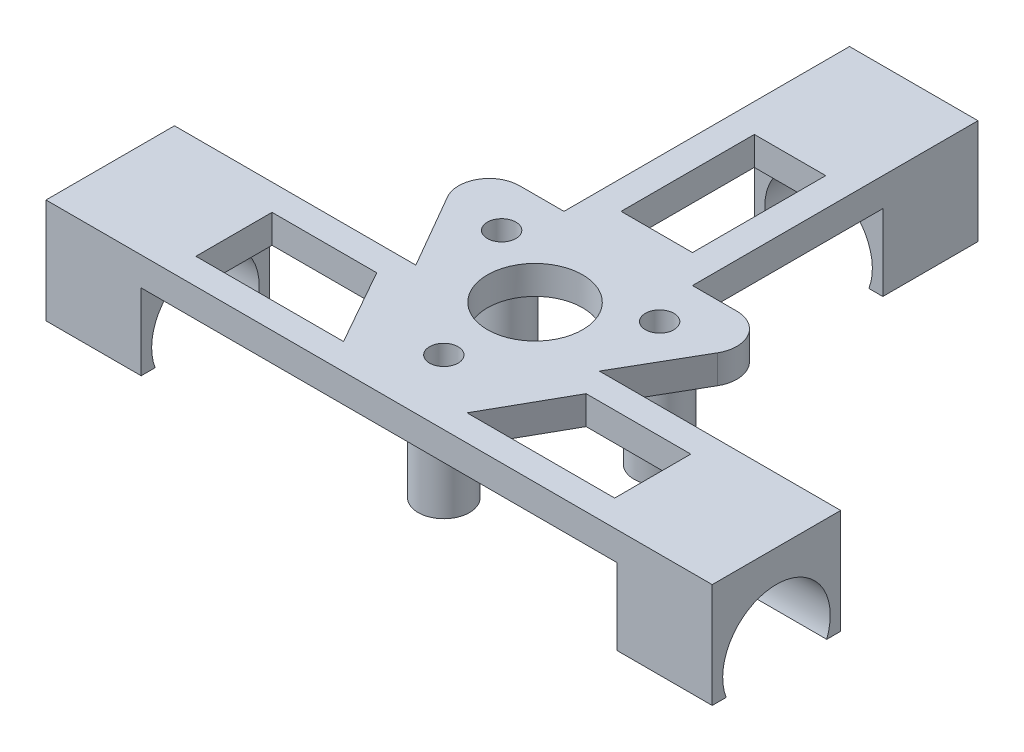
SolidWorks part; units mm, degrees
ref_plane "Front Plane" through (0, 0, 0) normal (0, 0, 1) x (1, 0, 0)
ref_plane "Top Plane" through (0, 0, 0) normal (0, 1, 0) x (1, 0, 0)
ref_plane "Right Plane" through (0, 0, 0) normal (1, 0, 0) x (0, 0, -1)
sketch "Sketch1" plane through (0, 0, 0) normal (0, 1, 0) x (1, 0, 0)
  line L0 (0, 0) -> (16.6, 0) construction
  line L1 (16.6, 0) -> (8.3, -14.376) construction
  line L2 (8.3, -14.376) -> (0, 0) construction
  line L3 (8.3, 0) -> (8.3, -14.376) construction
  line L4 (-3.1177, 5) -> (19.7177, 5)
  line L5 (22.489, 0.2) -> (11.0713, -19.576)
  line L6 (5.5287, -19.576) -> (-5.889, 0.2)
  line L7 (25.2603, 5) -> (8.3, -24.376) construction
  line L8 (8.3, -24.376) -> (-8.6603, 5) construction
  line L9 (-8.6603, 5) -> (25.2603, 5) construction
  circle A0 centre (0, 0) radius 1.5
  circle A1 centre (16.6, 0) radius 1.5
  circle A2 centre (8.3, -14.376) radius 1.5
  arc A3 (11.0713, -19.576) -> (5.5287, -19.576) centre (8.3, -17.976) cw
  arc A4 (22.489, 0.2) -> (19.7177, 5) centre (19.7177, 1.8) ccw
  arc A5 (-5.889, 0.2) -> (-3.1177, 5) centre (-3.1177, 1.8) cw
  dimension "D3" = 3
  dimension "D4" = 3
  dimension "D5" = 3
  dimension "D7" = 3.2
  dimension "D1" = 16.6
  dimension "D2" = 16.6
  dimension "D6" = 5
extrude "Caster Base" add sketch "Sketch1" along normal blind 3
sketch "Sketch2" plane through (0, 0, 0) normal (0, -1, 0) x (1, 0, 0)
  circle A0 centre (8.3, 14.376) radius 2.7
  circle A1 centre (0, 0) radius 2.7
  circle A2 centre (16.6, 0) radius 2.7
  circle A3 centre (8.3, 14.376) radius 1.6
  circle A4 centre (0, 0) radius 1.6
  circle A5 centre (16.6, 0) radius 1.6
  dimension "D1" = 5.4
  dimension "D2" = 5.4
  dimension "D3" = 5.4
extrude "Caster Standoffs" add sketch "Sketch2" along normal blind 10
sketch "Sketch3" plane through (0, 3, 0) normal (0, 1, 0) x (1, 0, 0)
  line L0 (8.3, 5) -> (8.3, -7.676) construction
  line L1 (-26.7, -21.176) -> (43.3, -21.176)
  line L2 (-26.7, -21.176) -> (-26.7, -7.676)
  line L3 (-26.7, -7.676) -> (43.3, -7.676)
  line L4 (43.3, -21.176) -> (43.3, -7.676)
  line L5 (19.7177, 5) -> (-3.1177, 5) construction
  arc A0 (5.5287, -19.576) -> (11.0713, -19.576) centre (8.3, -17.976) ccw construction
  circle A1 centre (8.3, -14.376) radius 1.6
  dimension "D1" = 70
  dimension "D2" = 13.5
extrude "Rear Arm" add sketch "Sketch3" against normal blind 3
sketch "Sketch4" plane through (0, 0, 0) normal (0, -1, 0) x (1, 0, 0)
  line L0 (-1.3417, 7.676) -> (-26.7, 7.676) construction
  line L1 (-26.7, 21.176) -> (-16.7, 21.176)
  line L2 (-26.7, 21.176) -> (-26.7, 7.676)
  line L3 (-26.7, 7.676) -> (-16.7, 7.676)
  line L4 (-16.7, 21.176) -> (-16.7, 7.676)
  line L5 (43.3, 7.676) -> (17.9417, 7.676) construction
  line L6 (43.3, 21.176) -> (33.3, 21.176)
  line L7 (43.3, 21.176) -> (43.3, 7.676)
  line L8 (43.3, 7.676) -> (33.3, 7.676)
  line L9 (33.3, 21.176) -> (33.3, 7.676)
  dimension "D1" = 10
  dimension "D2" = 10
extrude "Boss-Extrude4" add sketch "Sketch4" along normal blind 8
sketch "Sketch5" plane through (-26.7, 0, 0) normal (-1, 0, 0) x (0, 0, 1)
  line L0 (14.426, 3) -> (14.426, -8) construction
  line L1 (7.676, 3) -> (21.176, 3) construction
  line L2 (21.176, -8) -> (7.676, -8) construction
  circle A0 centre (14.426, -6) radius 5.65
  dimension "D1" = 11.3
  dimension "D2" = 2
extrude "Rear Inductor Clip 1" cut sketch "Sketch5" against normal up to surface (10 mm away) up to face at (-16.7, -4, 14.426)
sketch "Sketch6" plane through (43.3, 0, 0) normal (1, 0, 0) x (0, 0, -1)
  line L0 (-14.426, 3) -> (-14.426, -8) construction
  line L1 (-21.176, 3) -> (-7.676, 3) construction
  line L2 (-7.676, -8) -> (-21.176, -8) construction
  circle A0 centre (-14.426, -6) radius 5.65
  dimension "D1" = 2
  dimension "D2" = 11.3
extrude "Rear Inductor Clip 2" cut sketch "Sketch6" against normal up to surface (10 mm away) up to face at (33.3, -4, 14.426)
sketch "Sketch7" plane through (0, 3, 0) normal (0, 1, 0) x (1, 0, 0)
  line L0 (0, 0) -> (16.6, 0) construction
  line L1 (8.3, 0) -> (8.3, -14.376) construction
  line L2 (0, 0) -> (8.3, -14.376) construction
  line L3 (16.6, 0) -> (4.15, -7.188) construction
  circle A0 centre (8.3, -4.792) radius 5
  dimension "D1" = 10
extrude "Cut-Extrude4" cut sketch "Sketch7" against normal up to next
sketch "Sketch8" plane through (0, 3, 0) normal (0, 1, 0) x (1, 0, 0)
  line L0 (19.7177, 5) -> (-3.1177, 5) construction
  line L1 (1.55, 5) -> (15.05, 5)
  line L2 (1.55, 5) -> (1.55, 35)
  line L3 (1.55, 35) -> (15.05, 35)
  line L4 (15.05, 5) -> (15.05, 35)
  line L5 (8.3, 35) -> (8.3, -4.792) construction
  dimension "D1" = 30
  dimension "D2" = 13.5
extrude "Front Arm" add sketch "Sketch8" against normal blind 3
sketch "Sketch9" plane through (0, 0, 0) normal (0, -1, 0) x (1, 0, 0)
  line L0 (1.55, -35) -> (1.55, -5) construction
  line L1 (15.05, -35) -> (1.55, -35)
  line L2 (15.05, -35) -> (15.05, -25)
  line L3 (15.05, -25) -> (1.55, -25)
  line L4 (1.55, -35) -> (1.55, -25)
  dimension "D1" = 10
extrude "Boss-Extrude6" add sketch "Sketch9" along normal blind 8
sketch "Sketch10" plane through (0, 0, -35) normal (0, 0, -1) x (-1, 0, 0)
  line L0 (-8.3, 3) -> (-8.3, -8) construction
  line L1 (-15.05, 3) -> (-1.55, 3) construction
  line L2 (-1.55, -8) -> (-15.05, -8) construction
  circle A0 centre (-8.3, -6) radius 5.65
  dimension "D2" = 11.3
  dimension "D1" = 2
extrude "Front Inductor Clip" cut sketch "Sketch10" against normal up to next
sketch "Sketch11" plane through (0, 3, 0) normal (0, 1, 0) x (1, 0, 0)
  line L0 (-13.7, -14.426) -> (-26.7, -14.426) construction
  line L1 (4.55, 22) -> (12.05, 22)
  line L2 (4.55, 22) -> (4.55, 8)
  line L3 (4.55, 8) -> (12.05, 8)
  line L4 (12.05, 22) -> (12.05, 8)
  line L5 (-13.7, -10.426) -> (-2.7, -10.426)
  line L6 (-13.7, -10.426) -> (-13.7, -18.426)
  line L7 (-13.7, -18.426) -> (1.8116, -18.426)
  line L8 (-2.7, -10.426) -> (1.8116, -18.426)
  line L9 (8.3, -21.176) -> (8.3, -4.792) construction
  line L10 (-26.7, -21.176) -> (43.3, -21.176) construction
  line L11 (19.3, -10.426) -> (14.7884, -18.426)
  line L12 (30.3, -18.426) -> (14.7884, -18.426)
  line L13 (-26.7, -7.676) -> (-26.7, -21.176) construction
  line L14 (30.3, -10.426) -> (30.3, -18.426)
  line L15 (30.3, -10.426) -> (19.3, -10.426)
  line L16 (1.55, 35) -> (1.55, 5) construction
  line L17 (15.05, 5) -> (15.05, 35) construction
  dimension "D1" = 3
  dimension "D2" = 11
  dimension "D3" = 15.5116
  dimension "D4" = 8
  dimension "D5" = 3
  dimension "D6" = 3
  dimension "D7" = 3
  dimension "D8" = 3
extrude "Through Holes" cut sketch "Sketch11" against normal up to next
equation "\"D2@Sketch1\"=\"D1@Sketch1\""
equation "\"D4@Sketch1\"=\"D3@Sketch1\""
equation "\"D5@Sketch1\"=\"D3@Sketch1\""
equation "\"D2@Sketch2\"=\"D1@Sketch2\""
equation "\"D3@Sketch2\"=\"D1@Sketch2\""
equation "\"D3@Sketch11\"=\"D2@Sketch11\"+(4.85/8.6)*\"D4@Sketch11\""
